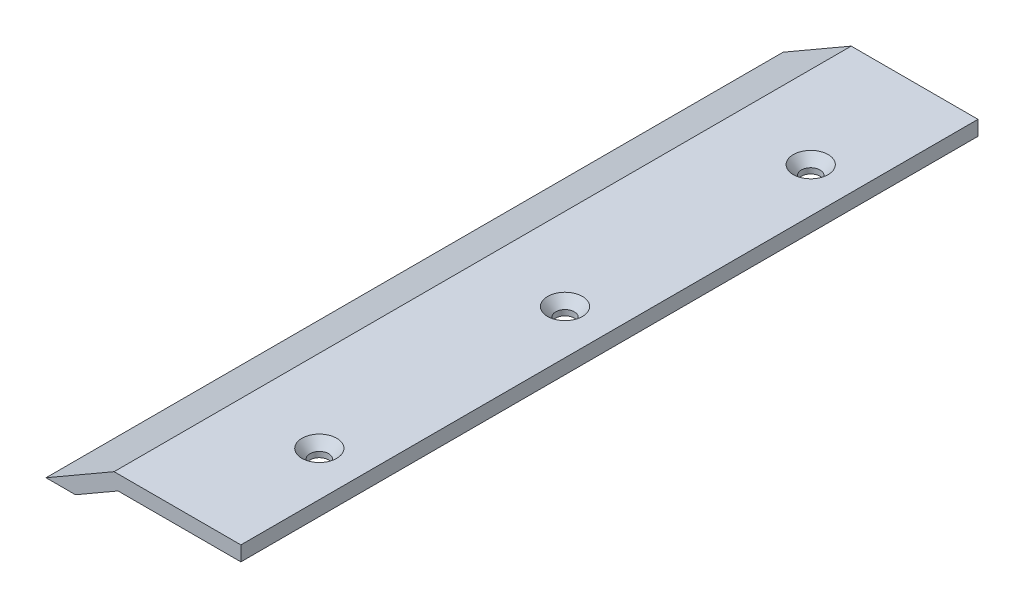
SolidWorks part; units mm, degrees
ref_plane "Alzado" through (0, 0, 0) normal (0, 0, 1) x (1, 0, 0)
ref_plane "Planta" through (0, 0, 0) normal (0, 1, 0) x (1, 0, 0)
ref_plane "Vista lateral" through (0, 0, 0) normal (1, 0, 0) x (0, 0, -1)
sketch "Croquis1" plane through (0, 0, 0) normal (0, 0, 1) x (1, 0, 0)
  line L1 (25, 0) -> (25, 3)
  line L2 (25, 3) -> (-0.8038, 3)
  line L3 (-0.8038, 3) -> (-14.6603, -5)
  line L4 (-14.6603, -5) -> (-8.6603, -5)
  line L5 (-8.6603, -5) -> (0, 0)
  line L7 (25, 0) -> (0, 0)
  line L8 (15.9597, 9.2216) -> (15.9597, -17.8486) construction
  dimension "D1" = 3
  dimension "D2" = 3
  dimension "D3" = 30
  dimension "D4" = 30.62
  dimension "D5" = 8
  dimension "D6" = 25
extrude "Saliente-Extruir1" add sketch "Croquis1" along normal mid plane 150
sketch "Croquis3" plane through (0, 3, 0) normal (0, 1, 0) x (1, 0, 0)
  line L0 (-61.5201, 0) -> (49.3842, 0) construction
  line L1 (-14.6603, -75) -> (-14.6603, 75) construction
  line L2 (15.9597, 0) -> (15.9597, 50) construction
  line L3 (15.9597, 0) -> (15.9597, -50) construction
  circle A0 centre (15.9597, 0) radius 1.9844
  circle A1 centre (15.9597, 50) radius 1.9844
  circle A2 centre (15.9597, -50) radius 1.9844
  dimension "D1" = 3.9688
  dimension "D2" = 30.62
  dimension "D4" = 50
  dimension "D6" = 50
  dimension "D3" = 2
  dimension "D5" = 2
hole_wizard "Avellanado para tornillo con cabeza ovalada de #61" positions "Croquis3D3" profile "Croquis4" countersink size "#6" standard "Ansi Inch"
sketch3d "Croquis3D3"
  point P0 (15.9597, 3, -50)
  point P3 (15.9597, 3, 0)
  point P6 (15.9597, 3, 50)
sketch "Croquis4" plane through (15.9597, 3, -50) normal (1, 0, 0) x (0, 0, 1)
  line L0 (0, 0) -> (0, 21.1408)
  line L1 (0, 21.1408) -> (1.8986, 20)
  line L2 (1.8986, 20) -> (1.8986, 1.892)
  line L3 (1.8986, 1.892) -> (3.5433, 0)
  line L5 (3.5433, 0) -> (0, 0)
  line L6 (-1.8986, 1.892) -> (-3.5433, 0) construction
  line L10 (0, 21.1408) -> (-1.8987, 20) construction
  line L11 (0, -6.35) -> (0, 107.95) construction
  dimension "Diámetro de taladro" = 3.7973
  dimension "Profundidad de taladro" = 20
  dimension "Ángulo de avellanado cercano" = 7.0866
  dimension "Ángulo de avellanado lejano" = 82
  dimension "Ángulo de perforador" = 118
